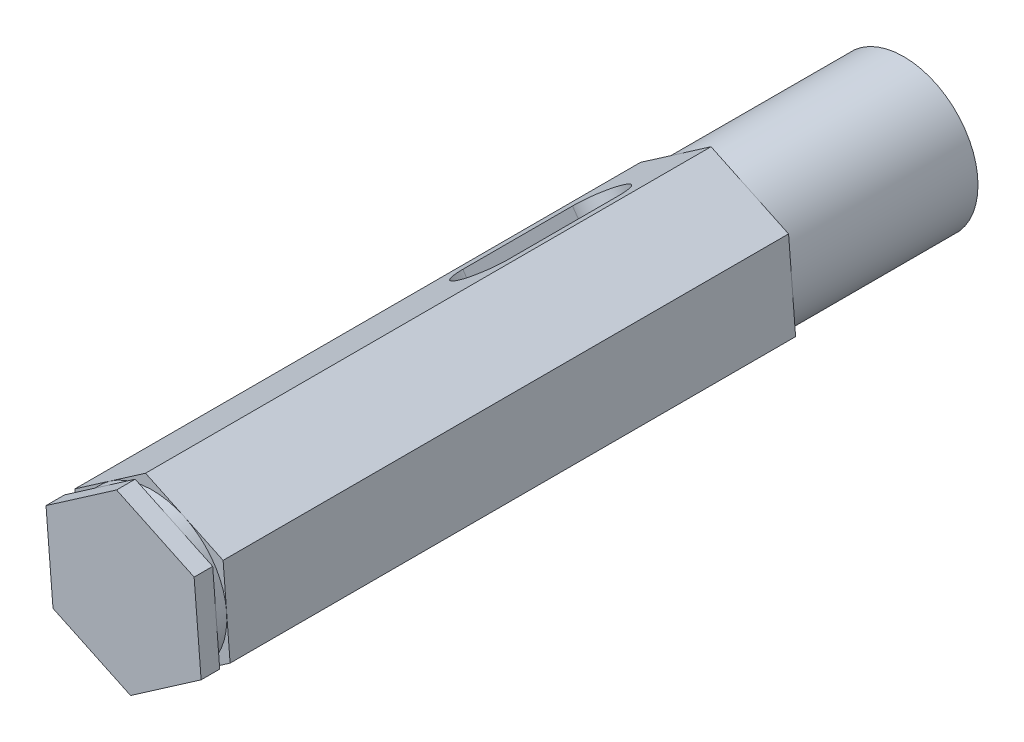
SolidWorks part; units mm, degrees
ref_plane "Front Plane" through (0, 0, 0) normal (0, 0, 1) x (1, 0, 0)
ref_plane "Top Plane" through (0, 0, 0) normal (0, 1, 0) x (1, 0, 0)
ref_plane "Right Plane" through (0, 0, 0) normal (1, 0, 0) x (0, 0, -1)
sketch "Sketch1" plane through (0, 0, 0) normal (0, 0, 1) x (1, 0, 0)
  line L1 (6.0296, 4.1722) -> (-0.5985, 7.3079)
  line L2 (-0.5985, 7.3079) -> (-6.6281, 3.1356)
  line L3 (-6.6281, 3.1356) -> (-6.0296, -4.1722)
  line L4 (-6.0296, -4.1722) -> (0.5985, -7.3079)
  line L5 (0.5985, -7.3079) -> (6.6281, -3.1356)
  line L6 (6.6281, -3.1356) -> (6.0296, 4.1722)
  circle A0 centre (0, 0) radius 6.35 construction
  circle A1 centre (0, 0) radius 2.7305
  dimension "D2" = 5.461
  dimension "D1" = 12.7
extrude "Boss-Extrude1" add sketch "Sketch1" along normal blind 20.9042
sketch "Sketch2" plane through (0, 0, 20.9042) normal (0, 0, 1) x (1, 0, 0)
  line L1 (-6.6281, 3.1356) -> (-6.0296, -4.1722)
  line L2 (-6.0296, -4.1722) -> (0.5985, -7.3079)
  line L3 (0.5985, -7.3079) -> (6.6281, -3.1356)
  line L4 (6.6281, -3.1356) -> (6.0296, 4.1722)
  line L5 (6.0296, 4.1722) -> (-0.5985, 7.3079)
  line L6 (-0.5985, 7.3079) -> (-6.6281, 3.1356)
  circle A0 centre (0, 0) radius 6.35 construction
extrude "Boss-Extrude2" add sketch "Sketch2" along normal blind 29.8958
sketch "Sketch3" plane through (0, 0, 0) normal (0, 0, -1) x (-1, 0, 0)
  circle A0 centre (0, 0) radius 6.3411
  circle A1 centre (0, 0) radius 2.7305
  dimension "D1" = 12.6822
  dimension "D2" = 5.461
extrude "Boss-Extrude3" add sketch "Sketch3" along normal blind 15.875
sketch "Sketch4" plane through (-3.6133, 5.2218, 0) normal (-0.569, 0.8223, 0) x (0.8223, 0.569, 0)
  line L0 (0, -16.2306) -> (0, -6.858) construction
  line L1 (-2.3876, -16.2306) -> (-2.3876, -6.858)
  line L2 (2.3876, -16.2306) -> (2.3876, -6.858)
  line L4 (3.6662, 0) -> (-3.6662, 0) construction
  line L5 (3.6662, -50.8) -> (-3.6662, -50.8) construction
  arc A0 (-2.3876, -16.2306) -> (2.3876, -16.2306) centre (0, -16.2306) ccw
  arc A1 (2.3876, -6.858) -> (-2.3876, -6.858) centre (0, -6.858) ccw
  point P3 (0, -11.5443)
  dimension "D1" = 2.3876
  dimension "D2" = 34.5694
  dimension "D3" = 6.858
extrude "Cut-Extrude1" cut sketch "Sketch4" against normal up to surface (12.7 mm away) up to face at (3.6133, -5.2218, 25.4)
ref_plane "Plane1" through (0, 0, 49.2125) normal (0, 0, 1) x (1, 0, 0)
sketch "Sketch5" plane through (0, 0, 49.2125) normal (0, 0, 1) x (1, 0, 0)
  circle A0 centre (0, 0) radius 7.62
  circle A1 centre (0, 0) radius 6.35
  dimension "D1" = 15.24
  dimension "D2" = 12.7
extrude "Cut-Extrude4" cut sketch "Sketch5" against normal blind 0.889
